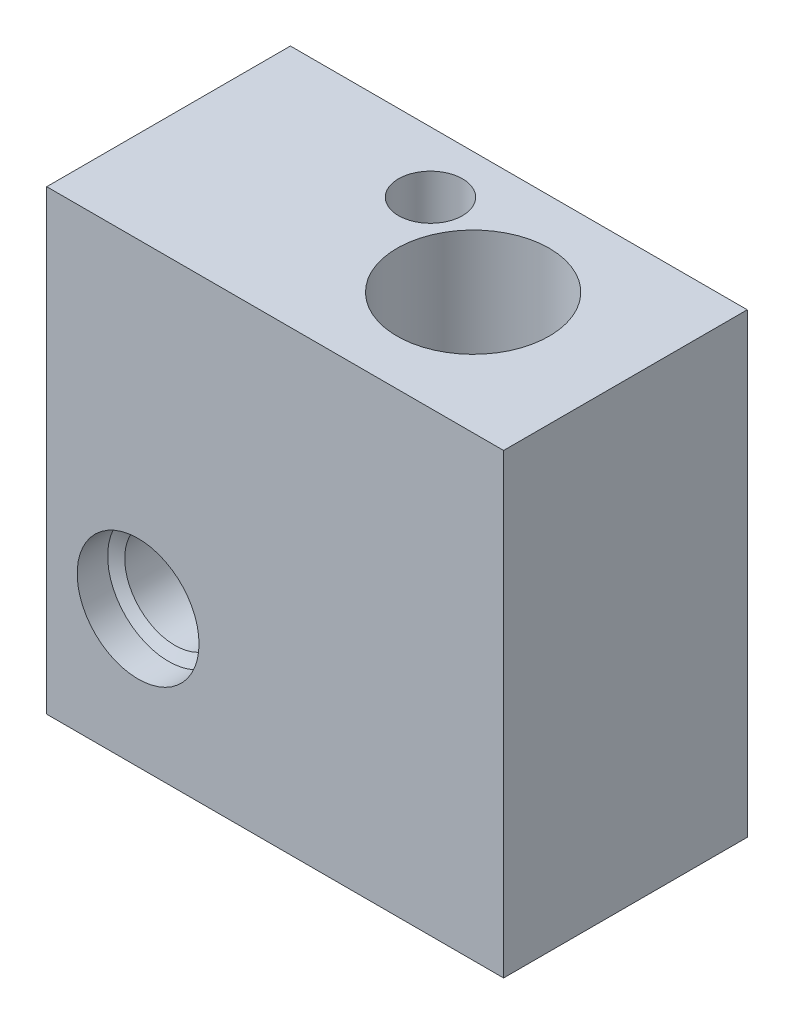
SolidWorks part; units mm, degrees
material "1060 Alloy"
ref_plane "Front Plane" through (0, 0, 0) normal (0, 0, 1) x (1, 0, 0)
ref_plane "Top Plane" through (0, 0, 0) normal (0, 1, 0) x (1, 0, 0)
ref_plane "Right Plane" through (0, 0, 0) normal (1, 0, 0) x (0, 0, -1)
sketch "Sketch1" plane through (0, 0, 0) normal (0, 0, 1) x (1, 0, 0)
  line L1 (-3, 10.5) -> (12, 10.5)
  line L2 (-3, 10.5) -> (-3, -4.5)
  line L3 (-3, -4.5) -> (12, -4.5)
  line L4 (12, 10.5) -> (12, -4.5)
  circle A0 centre (0, 0) radius 1.65
  dimension "D1" = 3.3
  dimension "D2" = 3
  dimension "D3" = 15
  dimension "D4" = 15
  dimension "D5" = 4.5
extrude "Boss-Extrude1" add sketch "Sketch1" along normal blind 8
cosmetic thread "Cosmetic Thread1" parameters "D2"=4
sketch "Sketch2" plane through (0, -4.5, 0) normal (0, -1, 0) x (1, 0, 0)
  line L0 (7, 4) -> (12, 4) construction
  line L1 (12, 8) -> (12, 0) construction
  circle A0 centre (7, 4) radius 2.5
  dimension "D1" = 5
  dimension "D2" = 7
extrude "Cut-Extrude1" cut sketch "Sketch2" against normal through all
sketch "Sketch3" plane through (0, -4.5, 0) normal (0, -1, 0) x (1, 0, 0)
  line L0 (-3, 0) -> (12, 0) construction
  line L1 (-3, 8) -> (-3, 0) construction
  circle A0 centre (3.6, 2) radius 1.05
  dimension "D1" = 2.1
  dimension "D3" = 6.6
  dimension "D2" = 2
extrude "Cut-Extrude2" cut sketch "Sketch3" against normal through all
hole_wizard "Ø4.0 (4) Diameter Hole1" positions "Sketch6" profile "Sketch5" hole size "Ø4.0" standard "ANSI Metric"
sketch "Sketch6" plane through (0, 0, 8) normal (0, 0, 1) x (1, 0, 0)
  point P0 (0, 0)
sketch "Sketch5" plane through (0, 0, 8) normal (1, 0, 0) x (0, -1, 0)
  line L0 (0, 0) -> (0, 2.2017)
  line L1 (0, 2.2017) -> (2, 1)
  line L2 (2, 1) -> (2, 0)
  line L5 (2, 0) -> (0, 0)
  line L10 (0, 2.2017) -> (-2, 1) construction
  line L11 (0, -6.35) -> (0, 107.95) construction
  dimension "Hole Dia." = 4
  dimension "Hole Depth" = 1
  dimension "Drill Angle" = 118
